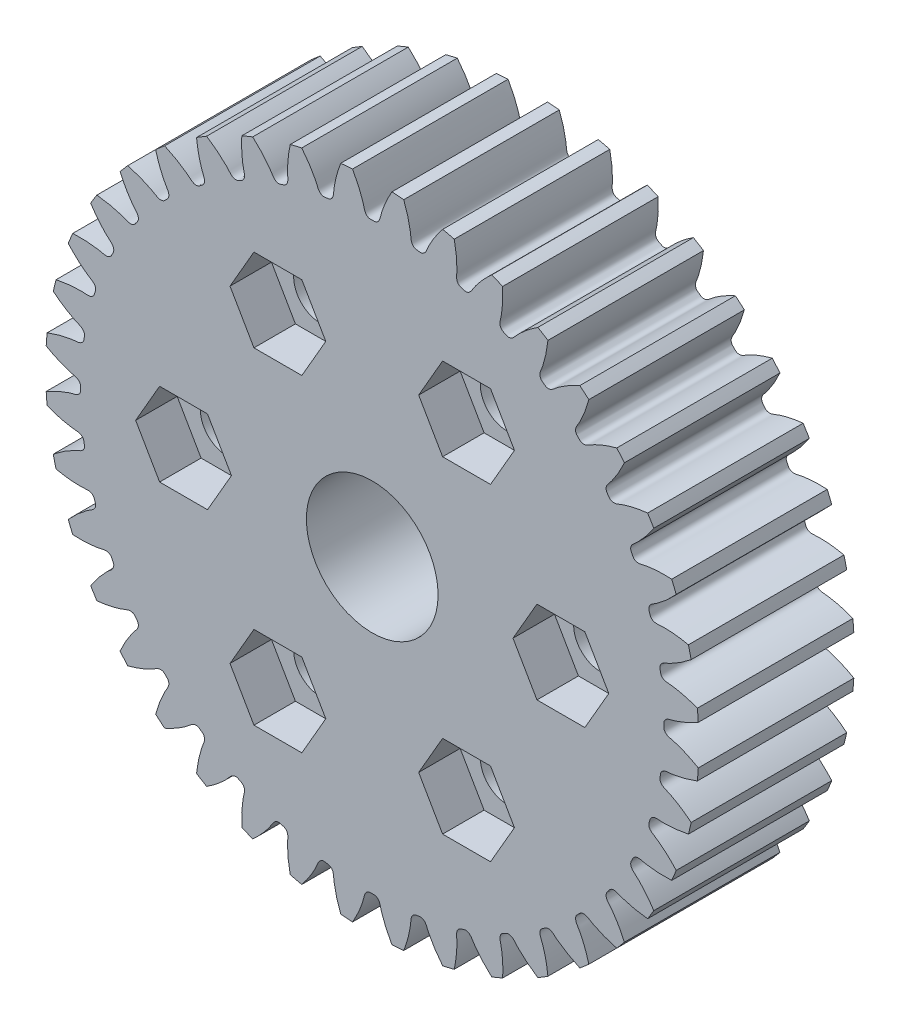
SolidWorks part; units mm, degrees
ref_plane "Front Plane" through (0, 0, 0) normal (0, 0, 1) x (1, 0, 0)
ref_plane "Top Plane" through (0, 0, 0) normal (0, 1, 0) x (1, 0, 0)
ref_plane "Right Plane" through (0, 0, 0) normal (1, 0, 0) x (0, 0, -1)
ref_axis "Axis1" through (0, 0, 55) along (0, 0, -1)
sketch "SketchRevolveSpurGear" plane through (0, 0, 0) normal (1, 0, 0) x (0, 0, -1)
  line L0 (0, 0) -> (1, 0) construction
  line L1 (-7.5, 0) -> (-7.5, 31.5)
  line L2 (-7.5, 31.5) -> (7.5, 31.5)
  line L3 (7.5, 31.5) -> (7.5, 0)
  line L4 (7.5, 0) -> (-7.5, 0)
  dimension "Side1" = 7.5
  dimension "OutsideRadius" = 31.5
  dimension "Side2" = 7.5
revolve "SpurGear" add sketch "SketchRevolveSpurGear" angle 360 about L0
sketch "SketchToothSpurGear" plane through (0, 0, 0) normal (0, 0, 1) x (1, 0, 0)
  arc A0 (31.5151, 1.9445) -> (31.5151, -1.9445) centre (0, 0) cw
  spline S0 degree 3 poles (31.5151, -1.9445) (31.375, -1.8626) (31.1666, -1.7455) (30.8899, -1.5998) (30.6923, -1.5002) (30.501, -1.408) (30.3161, -1.3229) (30.1379, -1.2447) (29.9666, -1.173) (29.8022, -1.1077) (29.645, -1.0484) (29.4951, -0.9949) (29.3527, -0.9469) (29.2179, -0.9041) (29.0909, -0.8662) (28.9717, -0.8331) (28.8258, -0.7946) (28.706, -0.7696) (28.614, -0.741) (28.5787, -0.7289) (28.5438, -0.7156) (28.5093, -0.701) (28.4749, -0.6849) (28.4406, -0.6669) (28.4061, -0.6466) (28.3712, -0.6236) (28.336, -0.597) (28.3004, -0.5661) (28.2647, -0.5299) (28.2295, -0.4871) (28.196, -0.4366) (28.1661, -0.3778) (28.1423, -0.3108) (28.1279, -0.2401) (28.122, -0.1356) (28.1271, 0) (28.122, 0.1356) (28.1279, 0.2401) (28.1423, 0.3108) (28.1661, 0.3778) (28.196, 0.4366) (28.2295, 0.4871) (28.2647, 0.5299) (28.3004, 0.5661) (28.336, 0.597) (28.3712, 0.6236) (28.4061, 0.6466) (28.4406, 0.6669) (28.4749, 0.6849) (28.5093, 0.701) (28.5438, 0.7156) (28.5787, 0.7289) (28.614, 0.741) (28.706, 0.7696) (28.8258, 0.7946) (28.9717, 0.8331) (29.0909, 0.8662) (29.2179, 0.9041) (29.3527, 0.9469) (29.4951, 0.9949) (29.645, 1.0484) (29.8022, 1.1077) (29.9666, 1.173) (30.1379, 1.2447) (30.3161, 1.3229) (30.501, 1.408) (30.6923, 1.5002) (30.8899, 1.5998) (31.1666, 1.7455) (31.375, 1.8626) (31.5151, 1.9445) knots 0 0 0 0 0.05894 0.086799 0.113584 0.139295 0.163932 0.187495 0.209984 0.231399 0.25174 0.271006 0.289199 0.306318 0.322363 0.337334 0.35123 0.377176 0.381719 0.386232 0.390736 0.395262 0.399843 0.404521 0.409345 0.414376 0.419685 0.425356 0.43148 0.438152 0.445453 0.45343 0.462059 0.471223 0.479506 0.5 0.520494 0.528777 0.537941 0.54657 0.554547 0.561848 0.56852 0.574644 0.580315 0.585624 0.590655 0.595479 0.600157 0.604738 0.609264 0.613768 0.618281 0.622824 0.64877 0.662666 0.677637 0.693682 0.710801 0.728994 0.74826 0.768601 0.790016 0.812505 0.836068 0.860705 0.886416 0.913201 0.94106 1 1 1 1
extrude "ToothExtrudeCutSpurGear" cut sketch "SketchToothSpurGear" against normal blind 7.5 and the other way blind 7.5
pattern_circular "PatternSpurGear" count 40 every 9 about axis through (0, 0, 55) along (0, 0, -1) of "ToothExtrudeCutSpurGear"
sketch "BoreRevolveSketch" plane through (0, 0, 0) normal (1, 0, 0) x (0, 0, -1)
  line L0 (0, 0) -> (1, 0) construction
  line L1 (-7.5, 0) -> (7.5, 0)
  line L2 (7.5, 0) -> (7.5, 6.35)
  line L3 (7.5, 6.35) -> (-7.5, 6.35)
  line L4 (-7.5, 6.35) -> (-7.5, 0)
  dimension "BoreSide1" = 7.5
  dimension "TaperSide1" = 6.35
  dimension "BoreSide2" = 7.5
  dimension "TaperSide2" = 6.35
revolve "BoreRevolveCut" cut sketch "BoreRevolveSketch" angle 360 about L0
sketch "AuxiliarySketchSpurGear" plane through (0, 0, 0) normal (0, 0, 1) x (1, 0, 0)
  circle A0 centre (0, 0) radius 30 construction
  circle A1 centre (0, 0) radius 28.1908 construction
  circle A2 centre (0, 0) radius 28.7502 construction
  circle A3 centre (0, 0) radius 31.5 construction
  circle A4 centre (0, 0) radius 28.125 construction
  dimension "PitchDiameter" = 60
  dimension "BaseDiameter" = 56.3816
  dimension "FormDiameter" = 57.5005
  dimension "MajorDiameter" = 63
  dimension "MinorDiameter" = 56.25
sketch "Sketch1" plane through (0, 0, 7.5) normal (0, 0, 1) x (1, 0, 0)
  line L0 (0, 0) -> (-18, 0) construction
  circle A0 centre (-18, 0) radius 2.575
  circle A1 centre (-9, 15.5885) radius 2.575
  circle A2 centre (9, 15.5885) radius 2.575
  circle A3 centre (18, 0) radius 2.575
  circle A4 centre (9, -15.5885) radius 2.575
  circle A5 centre (-9, -15.5885) radius 2.575
  point P16 (0, 0)
  dimension "D2" = 5.15
  dimension "D1" = 18
  dimension "D3" = 6
extrude "Cut-Extrude1" cut sketch "Sketch1" against normal blind 15
sketch "Sketch2" plane through (0, 0, 7.5) normal (0, 0, 1) x (1, 0, 0)
  line L0 (0, 0) -> (18.1949, 0) construction
  line L1 (11.4068, -11.7572) -> (6.788, -11.7572)
  line L2 (20.5043, -4) -> (22.8137, 0)
  line L3 (22.8137, 0) -> (20.5043, 4)
  line L4 (20.5043, 4) -> (15.8855, 4)
  line L5 (15.8855, 4) -> (13.5761, 0)
  line L6 (13.5761, 0) -> (15.8855, -4)
  line L7 (15.8855, -4) -> (20.5043, -4)
  line L8 (11.4068, -19.7572) -> (13.7162, -15.7572)
  line L9 (13.7162, -15.7572) -> (11.4068, -11.7572)
  line L10 (4.4786, -15.7572) -> (6.788, -19.7572)
  line L11 (6.788, -11.7572) -> (4.4786, -15.7572)
  line L12 (6.788, -19.7572) -> (11.4068, -19.7572)
  line L13 (-4.4786, -15.7572) -> (-6.788, -11.7572)
  line L14 (-11.4068, -19.7572) -> (-6.788, -19.7572)
  line L15 (-6.788, -19.7572) -> (-4.4786, -15.7572)
  line L16 (-11.4068, -11.7572) -> (-13.7162, -15.7572)
  line L17 (-6.788, -11.7572) -> (-11.4068, -11.7572)
  line L18 (-13.7162, -15.7572) -> (-11.4068, -19.7572)
  line L19 (-15.8855, -4) -> (-13.5761, 0)
  line L20 (-22.8137, 0) -> (-20.5043, -4)
  line L21 (-20.5043, -4) -> (-15.8855, -4)
  line L22 (-15.8855, 4) -> (-20.5043, 4)
  line L23 (-13.5761, 0) -> (-15.8855, 4)
  line L24 (-20.5043, 4) -> (-22.8137, 0)
  line L25 (-11.4068, 11.7572) -> (-6.788, 11.7572)
  line L26 (-11.4068, 19.7572) -> (-13.7162, 15.7572)
  line L27 (-13.7162, 15.7572) -> (-11.4068, 11.7572)
  line L28 (-4.4786, 15.7572) -> (-6.788, 19.7572)
  line L29 (-6.788, 11.7572) -> (-4.4786, 15.7572)
  line L30 (-6.788, 19.7572) -> (-11.4068, 19.7572)
  line L31 (4.4786, 15.7572) -> (6.788, 11.7572)
  line L32 (11.4068, 19.7572) -> (6.788, 19.7572)
  line L33 (6.788, 19.7572) -> (4.4786, 15.7572)
  line L34 (11.4068, 11.7572) -> (13.7162, 15.7572)
  line L35 (6.788, 11.7572) -> (11.4068, 11.7572)
  line L36 (13.7162, 15.7572) -> (11.4068, 19.7572)
  circle A0 centre (18.1949, 0) radius 4 construction
  circle A1 centre (9.0974, -15.7572) radius 4 construction
  circle A2 centre (-9.0974, -15.7572) radius 4 construction
  circle A3 centre (-18.1949, 0) radius 4 construction
  circle A4 centre (-9.0974, 15.7572) radius 4 construction
  circle A5 centre (9.0974, 15.7572) radius 4 construction
  point P52 (0, 0)
  dimension "D1" = 8
  dimension "D2" = 8
  dimension "D3" = 6
extrude "Cut-Extrude2" cut sketch "Sketch2" against normal blind 4
